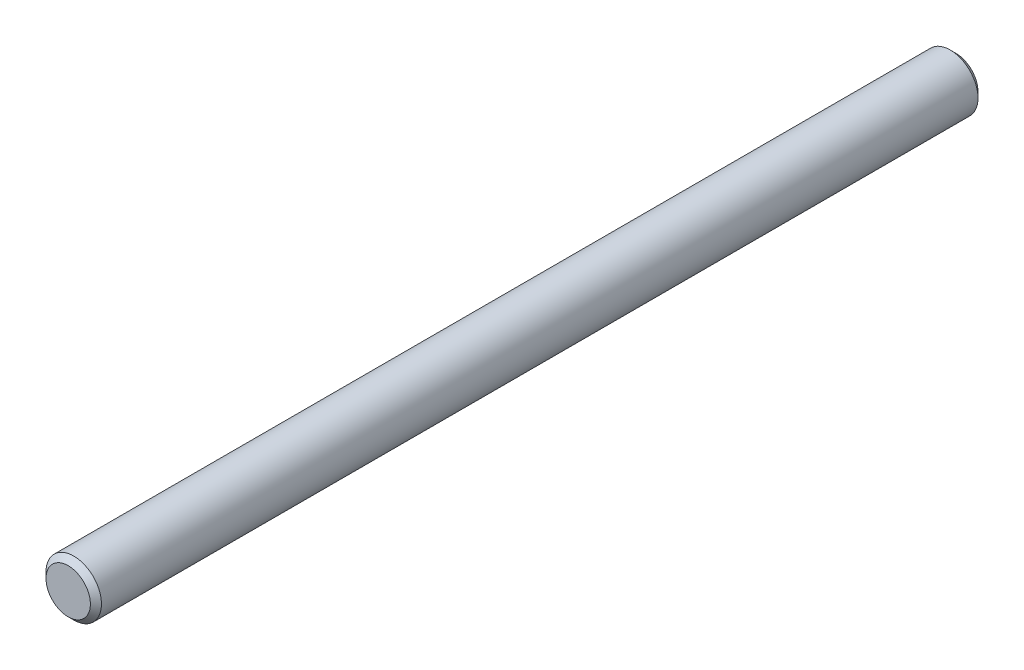
SolidWorks part; units mm, degrees
material "Plain Carbon Steel"
ref_plane "Front" through (0, 0, 0) normal (0, 0, 1) x (1, 0, 0)
ref_plane "Top" through (0, 0, 0) normal (0, 1, 0) x (1, 0, 0)
ref_plane "Right" through (0, 0, 0) normal (1, 0, 0) x (0, 0, -1)
sketch "Sketch1" plane through (0, 0, 0) normal (0, 0, 1) x (1, 0, 0)
  circle A0 centre (0, 0) radius 9.525
  dimension "dia" = 19.05
extrude "Extrude1" add sketch "Sketch1" along normal mid plane 304.8
sketch "Sketch2" plane through (0, 0, 0) normal (1, 0, 0) x (0, 0, -1)
  line L0 (152.4, 9.525) -> (149.86, 9.525) construction
  line L1 (152.4, 9.525) -> (-152.4, 9.525) construction
  line L2 (149.86, 9.525) -> (118.9037, 9.525) construction
  line L3 (118.9037, 9.525) -> (111.76, 9.525) construction
  line L4 (111.76, 9.525) -> (109.22, 9.525) construction
  line L5 (109.22, 9.525) -> (106.5632, 9.525) construction
  line L7 (97.6732, 9.525) -> (91.3232, 9.525) construction
  line L8 (91.3232, 9.525) -> (82.4332, 9.525) construction
  line L10 (-152.4, -9.525) -> (152.4, -9.525) construction
  line L11 (-152.4, 9.525) -> (-149.86, 9.525) construction
  line L12 (-149.86, 9.525) -> (-149.86, -9.525) construction
  line L13 (106.5632, 9.525) -> (97.6732, 9.525) construction
  line L14 (97.6732, 9.525) -> (97.6732, -9.525) construction
  line L15 (111.76, 9.525) -> (111.76, -9.525) construction
  line L16 (82.4332, 9.525) -> (76.0832, 9.525) construction
  line L17 (76.0832, 9.525) -> (67.1932, 9.525) construction
  line L18 (67.1932, 9.525) -> (60.8432, 9.525) construction
  line L19 (60.8432, 9.525) -> (51.9532, 9.525) construction
  line L20 (82.4332, 9.525) -> (82.4332, -9.525) construction
  line L21 (67.1932, 9.525) -> (67.1932, -9.525) construction
  line L22 (51.9532, 9.525) -> (51.9532, -9.525) construction
  line L23 (51.9532, 9.525) -> (45.6032, 9.525) construction
  line L24 (45.6032, 9.525) -> (36.7132, 9.525) construction
  line L25 (36.7132, 9.525) -> (36.7132, -9.525) construction
  line L26 (36.7132, 9.525) -> (30.3632, 9.525) construction
  line L27 (30.3632, 9.525) -> (21.4732, 9.525) construction
  line L28 (21.4732, 9.525) -> (15.1232, 9.525) construction
  line L29 (15.1232, 9.525) -> (6.2332, 9.525) construction
  line L30 (21.4732, 9.525) -> (21.4732, -9.525) construction
  line L31 (6.2332, 9.525) -> (6.2332, -9.525) construction
  line L32 (6.2332, 9.525) -> (-0.1168, 9.525) construction
  line L33 (-0.1168, 9.525) -> (-9.0068, 9.525) construction
  line L34 (-9.0068, 9.525) -> (-11.6637, 9.525) construction
  line L35 (-11.6637, 9.525) -> (-14.2037, 9.525) construction
  line L36 (-14.2037, 9.525) -> (-14.2037, -9.525) construction
  line L37 (-14.2037, 9.525) -> (-103.1037, 9.525) construction
  line L38 (-103.1037, 9.525) -> (-103.1037, -9.525) construction
  line L39 (109.22, 9.525) -> (109.22, -9.525) construction
  point P0 (-152.4, 9.525)
  point P1 (152.4, 9.525)
  dimension "D1" = 2.54
  dimension "D2" = 30.9562
  dimension "D3" = 7.1437
  dimension "D4" = 2.54
  dimension "D5" = 2.6568
  dimension "D6" = 8.89
  dimension "D7" = 8.89
  dimension "D8" = 2.54
  dimension "D9" = 6.35
  dimension "D10" = 6.35
  dimension "D11" = 8.89
  dimension "D12" = 6.35
  dimension "D13" = 8.89
  dimension "D14" = 6.35
  dimension "D15" = 8.89
  dimension "D16" = 6.35
  dimension "D17" = 8.89
  dimension "D18" = 6.35
  dimension "D19" = 8.89
  dimension "D20" = 6.35
  dimension "D21" = 8.89
  dimension "D22" = 2.6568
  dimension "D23" = 2.54
  dimension "D24" = 88.9
chamfer "Chamfer1" distance 1.905 angle 45 2 edges at (9.525, 0, -152.4) (9.525, 0, 152.4)
equation "\"D1@Chamfer1\" = \"dia@Sketch1\" * .1"
